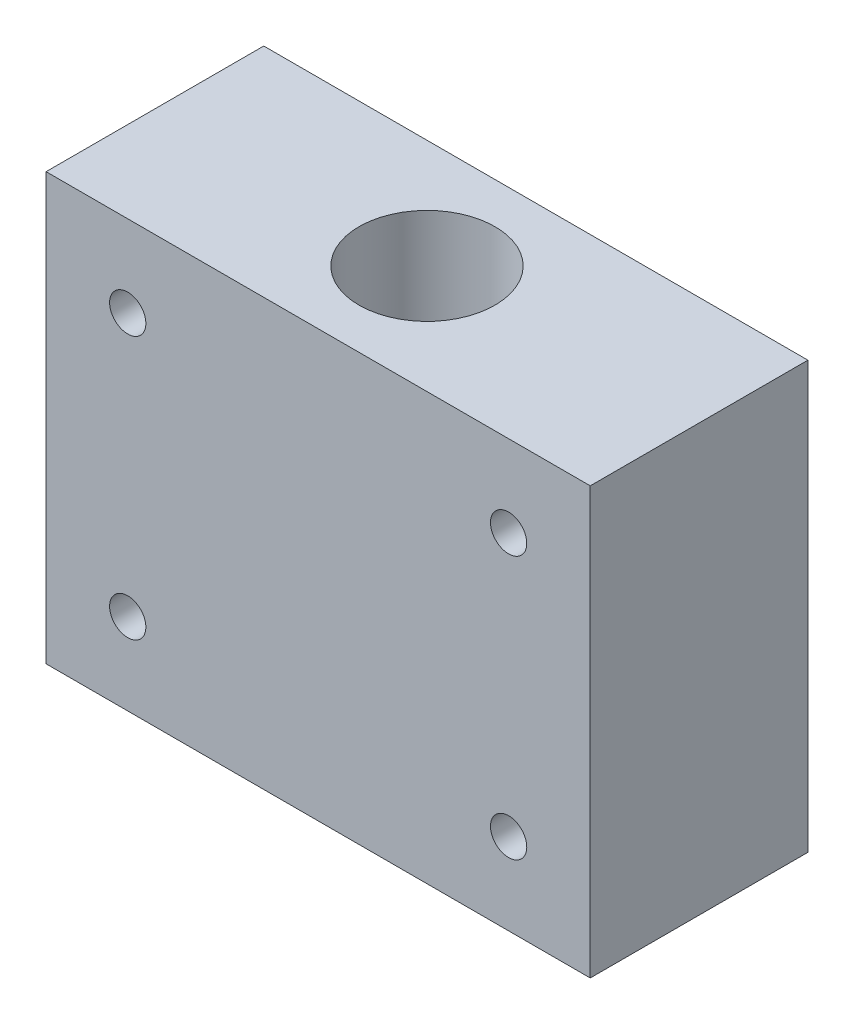
SolidWorks part; units mm, degrees
ref_plane "Front Plane" through (0, 0, 0) normal (0, 0, 1) x (1, 0, 0)
ref_plane "Top Plane" through (0, 0, 0) normal (0, 1, 0) x (1, 0, 0)
ref_plane "Right Plane" through (0, 0, 0) normal (1, 0, 0) x (0, 0, -1)
sketch "Sketch2" plane through (0, 0, 0) normal (0, 1, 0) x (1, 0, 0)
  line L1 (-30, -12) -> (30, -12)
  line L2 (-30, -12) -> (-30, 12)
  line L3 (-30, 12) -> (30, 12)
  line L4 (30, -12) -> (30, 12)
  line L5 (-30, -12) -> (30, 12) construction
  line L6 (-30, 12) -> (30, -12) construction
  circle A0 centre (0, 0) radius 7.5
  point P0 (0, 0)
  dimension "D3" = 15
  dimension "D1" = 60
  dimension "D2" = 24
extrude "Boss-Extrude1" add sketch "Sketch2" along normal blind 47
sketch "Sketch7" plane through (0, 47, 0) normal (0, 1, 0) x (1, 0, 0)
extrude "Boss-Extrude2" add sketch "Sketch2<2>" along normal blind 25.5
sketch "Sketch2<2>" plane through (0, 0, 0) normal (0, 1, 0) x (1, 0, 0) same geometry as "Sketch2"
sketch "Sketch8" plane through (0, 0, 12) normal (0, 0, 1) x (1, 0, 0)
  line L0 (-21, 9) -> (21, 9) construction
  line L1 (21, 9) -> (21, 38) construction
  line L2 (21, 38) -> (-21, 38) construction
  line L3 (-21, 38) -> (-21, 9) construction
  circle A0 centre (-21, 9) radius 2
  circle A1 centre (-21, 38) radius 2
  circle A2 centre (21, 38) radius 2
  circle A3 centre (21, 9) radius 2
  dimension "D1" = 4
extrude "Cut-Extrude1" cut sketch "Sketch8" against normal through all
